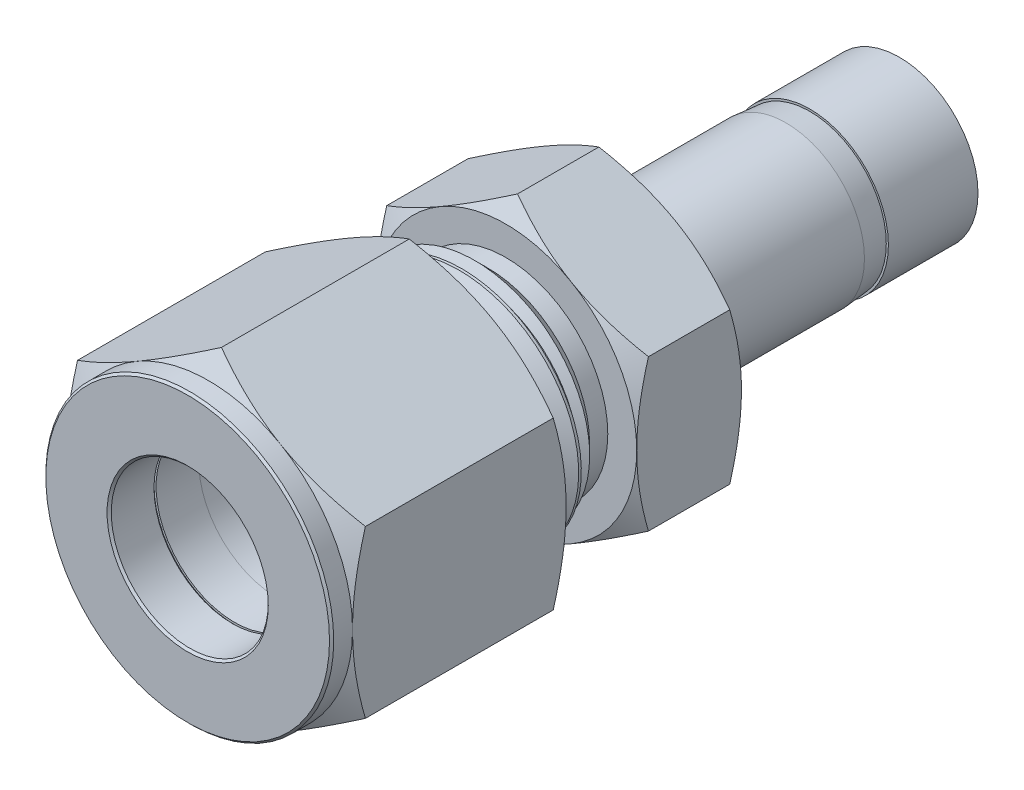
SolidWorks part; units mm, degrees
ref_plane "Front Plane" through (0, 0, 0) normal (0, 0, 1) x (1, 0, 0)
ref_plane "Top Plane" through (0, 0, 0) normal (0, 1, 0) x (1, 0, 0)
ref_plane "Right Plane" through (0, 0, 0) normal (1, 0, 0) x (0, 0, -1)
sketch "Sketch1" plane through (0, 0, 0) normal (1, 0, 0) x (0, 0, -1)
  line L0 (0, 0) -> (43.18, 0) construction
  line L1 (0, 4.7625) -> (0, -4.7625) construction
  line L2 (14.224, 8.7312) -> (14.224, -8.7312) construction
  line L3 (5.6896, 7.1437) -> (5.6896, -7.1437) construction
  line L4 (5.6896, 7.1437) -> (5.6896, 5.8737) construction
  line L6 (4.7625, 6.2865) -> (9.6393, 5.08) construction
  line L7 (9.6393, 5.08) -> (9.6393, 4.7625) construction
  line L8 (9.6393, 4.7625) -> (5.4356, 4.7625) construction
  line L9 (5.4356, 4.7625) -> (4.7625, 5.4356) construction
  line L10 (4.7625, 5.4356) -> (4.7625, 6.2865) construction
  line L11 (2.8448, 6.223) -> (3.9878, 6.223) construction
  line L12 (3.9878, 6.223) -> (3.9878, 5.4356) construction
  line L13 (3.9878, 5.4356) -> (4.7625, 5.4356) construction
  line L14 (25.654, 3.556) -> (25.654, -3.556) construction
  line L15 (4.7625, 5.4356) -> (4.7625, 4.7625) construction
  line L16 (5.4356, 4.7625) -> (2.8448, 4.7625) construction
  line L17 (2.8448, 4.7625) -> (2.8448, 6.223) construction
  line L18 (4.7625, 4.7625) -> (5.4356, 4.7625) construction
  line L19 (0, 4.7625) -> (2.8448, 4.7625) construction
  line L20 (2.8448, 4.7625) -> (5.6896, 4.7625) construction
  line L22 (19.304, 7.9375) -> (19.304, -7.9375) construction
  line L23 (37.7444, 4.7625) -> (43.18, 4.7625) construction
  line L24 (43.18, 4.7625) -> (43.18, -4.7625) construction
  point P4 (1.27, 0)
  point P10 (5.6896, 0)
  point P12 (14.224, 0)
  point P15 (19.304, 0)
  point P16 (7.366, 0)
  point P17 (17.018, 0)
  point P33 (25.654, 0)
  dimension "BF OD 2" = 12.446
  dimension "BF Lg" = 2.5908
  dimension "BF Lg 1" = 1.143
  dimension "FF Lg" = 4.8768
  dimension "FF OD 1" = 10.16
  dimension "FF OD 2" = 12.573
  dimension "BF OD 1" = 10.8712
  dimension "Nut Lg" = 14.224
  dimension "Tube OD" = 9.525
  dimension "Nut Hex" = 17.4625
  dimension "Straight Thread OD" = 14.2875
  dimension "Nut Thread Lg" = 8.5344
  dimension "Straight Thread Pitch" = 1.27
  dimension "Lg 1" = 1.27
  dimension "Lg" = 43.18
  dimension "Body Hex" = 15.875
  dimension "C" = 19.304
  dimension "D" = 35.814
  dimension "Insertion Depth" = 17.018
  dimension "E" = 7.112
  dimension "K" = 17.526
  dimension "Stem OD" = 9.525
  dimension "L1" = 5.4356
sketch "Sketch2" plane through (0, 0, 0) normal (0, 0, 1) x (1, 0, 0)
  line L0 (0, 4.7625) -> (0, -4.7625) construction
  line L1 (0, 10.082) -> (-8.7312, 5.041)
  line L2 (-8.7312, 5.041) -> (-8.7312, -5.041)
  line L3 (-8.7312, -5.041) -> (0, -10.082)
  line L4 (0, -10.082) -> (8.7312, -5.041)
  line L5 (8.7312, -5.041) -> (8.7313, 5.041)
  line L6 (8.7313, 5.041) -> (0, 10.082)
  line L7 (0, 10.082) -> (0, 0) construction
  circle A0 centre (0, 0) radius 8.7312 construction
extrude "Boss-Extrude1" add sketch "Sketch2" against normal up to vertex (14.224 mm away) up to point (0, 0, -14.224)
sketch "Sketch3" plane through (0, 0, 0) normal (1, 0, 0) x (0, 0, -1)
  line L0 (0, 10.082) -> (0, 8.7312)
  line L1 (0, 5.041) -> (0, 10.082) construction
  line L2 (0, 8.7312) -> (1.27, 8.7312)
  line L3 (1.27, 8.7312) -> (2.0498, 10.082)
  line L4 (14.224, 10.082) -> (0, 10.082) construction
  line L5 (2.0498, 10.082) -> (13.4442, 10.082)
  line L6 (13.4442, 10.082) -> (14.224, 8.7312)
  line L7 (14.224, 8.7312) -> (14.224, 10.082)
  line L8 (14.224, 10.082) -> (14.224, 11.4327)
  line L9 (14.224, 11.4327) -> (0, 11.4327)
  line L10 (0, 11.4327) -> (0, 10.082)
  line L11 (0, 4.7625) -> (0, 0)
  line L12 (0, 4.7625) -> (0, -4.7625) construction
  line L13 (0, 0) -> (14.224, 0)
  line L14 (14.224, 8.7312) -> (14.224, -8.7312) construction
  line L15 (14.224, 0) -> (14.224, 7.1437)
  line L16 (14.224, 7.1437) -> (5.6896, 7.1437)
  line L17 (5.6896, 7.1437) -> (5.6896, 5.8737) construction
  line L18 (5.6896, 5.8737) -> (2.8448, 5.8737) construction
  line L19 (2.8448, 5.8737) -> (2.8448, 4.7625)
  line L20 (2.8448, 4.7625) -> (0, 4.7625)
  line L21 (2.8448, 5.8737) -> (2.8448, 7.1437) construction
  line L22 (2.8448, 7.1437) -> (5.6896, 7.1437) construction
  line L23 (5.6896, 6.5087) -> (2.8448, 6.5087)
  line L24 (2.8448, 6.5087) -> (2.8448, 5.8737)
  line L25 (5.6896, 6.5087) -> (5.6896, 7.1437)
  dimension "D1" = 30
  dimension "D2" = 1.27
revolve "Cut-Revolve1" cut sketch "Sketch3" angle 360 about L0
chamfer "Chamfer1" distance 0.127 angle 45 3 edges at (4.7625, 0, -2.8448) (4.7625, 0, 0) (8.7312, 0, 0)
sketch "Sketch4" plane through (0, 0, 0) normal (1, 0, 0) x (0, 0, -1)
  line L1 (19.304, 0) -> (7.366, 0)
  line L2 (19.304, 0) -> (19.304, 7.1438)
  line L3 (19.304, 7.1438) -> (7.366, 7.1437)
  line L4 (7.366, 0) -> (7.366, 7.1437)
  dimension "D1" = 11.938
revolve "Revolve1" add sketch "Sketch4" angle 360 about L1
sketch "Sketch5" plane through (0, 0, -7.366) normal (0, 0, -1) x (-1, 0, 0)
  circle A0 centre (0, 0) radius 7.1437 construction
  circle A1 centre (0, 0) radius 7.1438
  point P3 (0, 7.1437)
curve "Helix/Spiral1" pitch 1.27 height 13.208 radius 7.1438 centre (0, 0, -7.366) axis (0, 0, -1) start towards (0, 1, 0)
sketch "Sketch6" plane through (0, 0, 0) normal (1, 0, 0) x (0, 0, -1)
  line L0 (6.1754, 7.2812) -> (7.4454, 7.2812) construction
  line L1 (7.4454, 7.2812) -> (6.8104, 6.1814) construction
  line L2 (6.8104, 6.1814) -> (6.1754, 7.2812) construction
  line L3 (6.731, 6.3189) -> (6.8897, 6.3189) construction
  line L4 (6.2547, 7.1437) -> (7.366, 7.1437) construction
  line L5 (6.8104, 6.1814) -> (6.8104, 6.3189) construction
  line L6 (6.8104, 7.1437) -> (6.8104, 7.2812) construction
  line L7 (6.731, 6.3189) -> (6.2151, 7.2125)
  line L8 (6.2151, 7.2125) -> (7.4057, 7.2125)
  line L9 (7.4057, 7.2125) -> (6.8897, 6.3189)
  line L10 (6.8897, 6.3189) -> (6.731, 6.3189)
  point P10 (6.8104, 7.2125)
  dimension "D1" = 1.27
  dimension "D2" = 0.1588
sweep "Cut-Sweep1" cut profiles "Sketch6" path "Helix/Spiral1"
sketch "Sketch7" plane through (0, 0, -19.304) normal (0, 0, -1) x (-1, 0, 0)
  line L0 (0, 0) -> (0, 9.1654) construction
  line L1 (0, 9.1654) -> (-7.9375, 4.5827)
  line L2 (-7.9375, 4.5827) -> (-7.9375, -4.5827)
  line L3 (-7.9375, -4.5827) -> (0, -9.1654)
  line L4 (0, -9.1654) -> (7.9375, -4.5827)
  line L5 (7.9375, -4.5827) -> (7.9375, 4.5827)
  line L6 (7.9375, 4.5827) -> (0, 9.1654)
  circle A0 centre (0, 0) radius 7.9375 construction
extrude "Boss-Extrude2" add sketch "Sketch7" along normal up to vertex (6.35 mm away) up to point (0, 0, -25.654)
sketch "Sketch8" plane through (0, 0, 0) normal (1, 0, 0) x (0, 0, -1)
  line L0 (7.366, 7.2812) -> (7.366, 6.1814)
  line L1 (7.366, 6.1814) -> (8.4659, 7.2812)
  line L2 (8.4659, 7.2812) -> (7.366, 7.2812)
  line L3 (19.304, 7.2812) -> (17.1043, 7.2812)
  line L4 (17.1043, 7.2812) -> (18.2041, 6.1814)
  line L5 (18.2041, 6.1814) -> (19.304, 6.1814)
  line L6 (19.304, 6.1814) -> (19.304, 7.2812)
  line L7 (19.304, 7.9375) -> (20.0129, 9.1654)
  line L9 (25.654, 9.1654) -> (19.304, 9.1654) construction
  line L10 (20.0129, 9.1654) -> (24.9451, 9.1654)
  line L11 (17.018, 3.556) -> (25.654, 3.556)
  line L12 (24.9451, 9.1654) -> (25.654, 7.9375)
  line L14 (25.654, 9.1654) -> (25.654, 10.3934)
  line L15 (25.654, 10.3934) -> (19.304, 10.3934)
  line L16 (19.304, 10.3934) -> (19.304, 9.1654)
  line L17 (19.304, 9.1654) -> (19.304, 7.9375)
  line L18 (6.8104, 6.1814) -> (7.366, 6.1814) construction
  line L19 (7.4454, 7.2812) -> (7.366, 7.2812) construction
  line L20 (8.4659, 7.2812) -> (17.1043, 7.2812) construction
  line L21 (18.2041, 6.1814) -> (7.366, 6.1814) construction
  line L22 (7.366, 5.6424) -> (10.9227, 4.7625)
  line L23 (25.654, 7.9375) -> (25.654, 9.1654)
  line L24 (7.366, 5.0514) -> (7.366, -6.3277) construction
  line L25 (4.7625, 6.2865) -> (9.6393, 5.08) construction
  line L26 (25.654, 0) -> (7.366, 0)
  line L27 (7.366, 0) -> (7.366, 5.6424)
  line L28 (10.9227, 4.7625) -> (17.018, 4.7625)
  line L29 (17.018, 4.7625) -> (17.018, 3.556)
  line L30 (25.654, 3.556) -> (25.654, 0)
  line L31 (17.018, 0) -> (17.018, 3.556) construction
  line L32 (19.304, 9.1654) -> (19.304, 4.5827) construction
  line L33 (25.654, 9.1654) -> (25.654, 4.5827) construction
  line L34 (25.654, 9.1654) -> (19.304, 9.1654) construction
  line L35 (19.304, 7.9375) -> (19.304, -7.9375) construction
  dimension "D1" = 30
revolve "Cut-Revolve2" cut sketch "Sketch8" angle 360 about L0
sketch "Sketch9" plane through (0, 0, 0) normal (1, 0, 0) x (0, 0, -1)
  line L0 (4.7625, 6.2865) -> (4.7625, 5.4356)
  line L1 (4.7625, 5.4356) -> (5.4356, 4.7625)
  line L2 (5.4356, 4.7625) -> (9.6393, 4.7625)
  line L3 (9.6393, 4.7625) -> (9.6393, 5.08)
  line L4 (9.6393, 5.08) -> (4.7625, 6.2865)
revolve "Revolve2" add sketch "Sketch9" angle 360 about L0
sketch "Sketch10" plane through (0, 0, 0) normal (1, 0, 0) x (0, 0, -1)
  line L0 (2.8448, 6.223) -> (3.9878, 6.223)
  line L1 (3.9878, 6.223) -> (3.9878, 5.4356)
  line L2 (3.9878, 5.4356) -> (4.7625, 5.4356)
  line L4 (4.7625, 5.4356) -> (5.4356, 4.7625)
  line L5 (5.4356, 4.7625) -> (2.8448, 4.7625)
  line L6 (2.8448, 4.7625) -> (2.8448, 6.223)
revolve "Revolve3" add sketch "Sketch10" angle 360 about L0
sketch "Sketch11" plane through (0, 0, 0) normal (1, 0, 0) x (0, 0, -1)
  line L0 (25.654, 3.556) -> (43.18, 3.556)
  line L1 (43.18, 3.556) -> (43.18, 4.7625)
  line L2 (43.18, 4.7625) -> (37.7444, 4.7625)
  line L3 (25.654, 4.7625) -> (25.654, 3.556)
  line L4 (37.7444, 4.7625) -> (37.7444, 4.6355)
  line L5 (37.7444, 4.6355) -> (36.2928, 4.7625)
  line L6 (36.2928, 4.7625) -> (25.654, 4.7625)
  dimension "D1" = 0.127
  dimension "D2" = 5
revolve "Revolve4" add sketch "Sketch11" angle 360 about L0
equation "\"D4@Helix/Spiral1\" = \"Straight Thread Pitch@Sketch1\""
equation "\"D3@Helix/Spiral1\" = \"D4@Helix/Spiral1\" + \"D1@Sketch4\""
equation "\"D1@Sketch6\" = \"D4@Helix/Spiral1\""
equation "\"D2@Sketch6\" = \"D1@Sketch6\" / 8"
